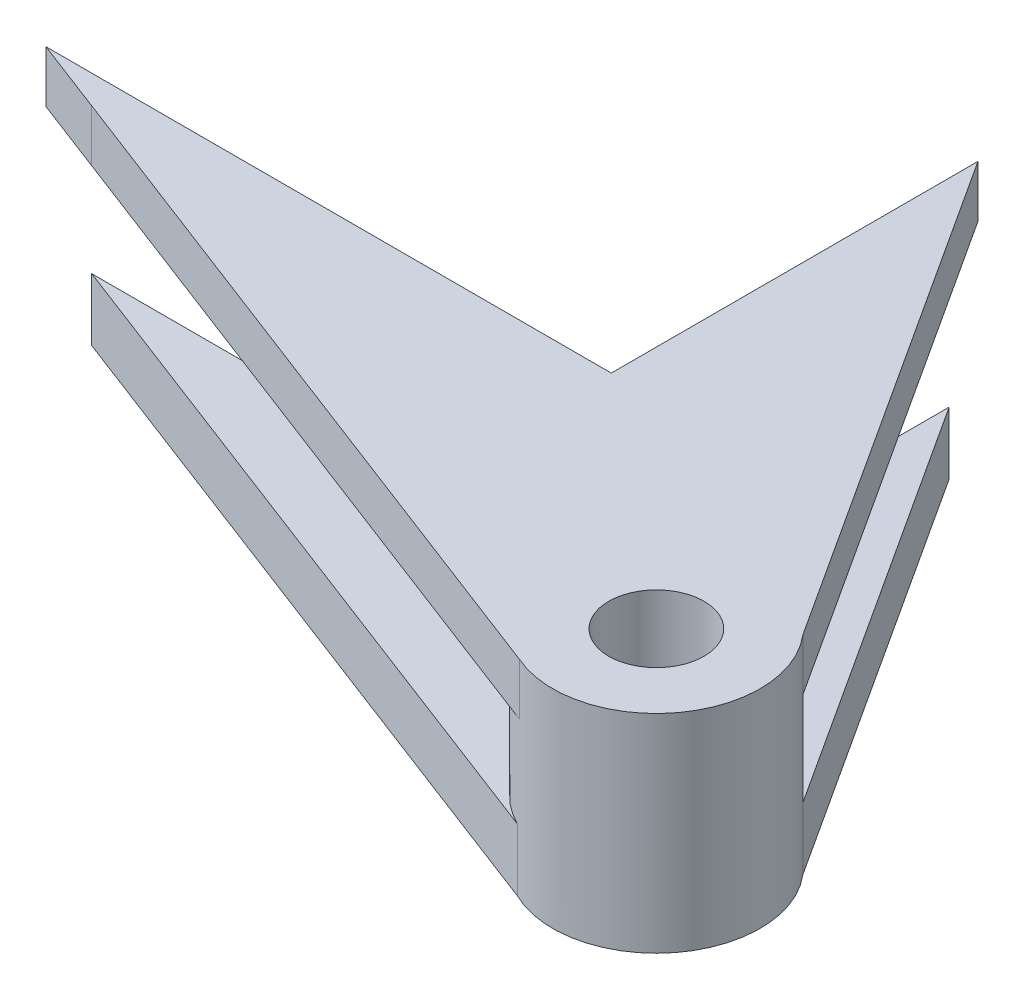
SolidWorks part; units mm, degrees
ref_plane "Front Plane" through (0, 0, 0) normal (0, 0, 1) x (1, 0, 0)
ref_plane "Top Plane" through (0, 0, 0) normal (0, 1, 0) x (1, 0, 0)
ref_plane "Right Plane" through (0, 0, 0) normal (1, 0, 0) x (0, 0, -1)
sketch "Sketch1" plane through (0, 0, 0) normal (0, 1, 0) x (1, 0, 0)
  line L0 (30.5988, 30.1673) -> (30.5988, 0)
  line L1 (30.5988, 30.1673) -> (56.5573, -9.8891)
  line L2 (0, 0) -> (-21.8247, 0)
  line L3 (-21.8247, 0) -> (44.5863, -25.4049)
  line L4 (30.5988, 0) -> (0, 0)
  circle A0 centre (48.9905, -16.427) radius 10
  circle A1 centre (48.9905, -16.427) radius 4.5901
  point P7 (58.0822, -8.6013)
  point P10 (45.2716, -23.9064)
  dimension "20" = 20
extrude "Boss-Extrude1" add sketch "Sketch1" along normal blind 6 contours A0 L1 L2 L3 region at (26.3214, 0, 2.862)
extrude "Boss-Extrude2" add sketch "Sketch1<3>" along normal blind 20 contours A0 A1 region at (58.0974, 0, 13.0376)
sketch "Sketch1<3>" plane through (0, 0, 0) normal (0, 1, 0) x (1, 0, 0) same geometry as "Sketch1"
sketch "Sketch2" plane through (0, 20, 0) normal (0, 1, 0) x (1, 0, 0)
  line L0 (56.5573, -9.8891) -> (30.5988, 30.1673)
  line L1 (30.5988, 30.1673) -> (25.4894, 38.0515)
  line L2 (25.4894, 38.0515) -> (25.4894, 2.7291)
  line L3 (25.4894, 2.7291) -> (-28.959, 2.7291)
  line L4 (-28.959, 2.7291) -> (-21.8247, 0)
  line L5 (-21.8247, 0) -> (44.5863, -25.4049) construction
  line L6 (-21.8247, 0) -> (45.9025, -25.9383)
  circle A0 centre (48.9905, -16.427) radius 10
  circle A1 centre (48.9905, -16.427) radius 10 construction
  point P16 (0, 0)
  point P17 (46.2996, -24.5677)
  point P20 (41.614, -12.947)
  circle M3 centre (48.9905, -16.427) radius 10
extrude "Boss-Extrude3" add sketch "Sketch2" against normal blind 5 contours L4 L6 L0 L1 L2 L3 M3 region at (23.9704, 20, 0.0322)
